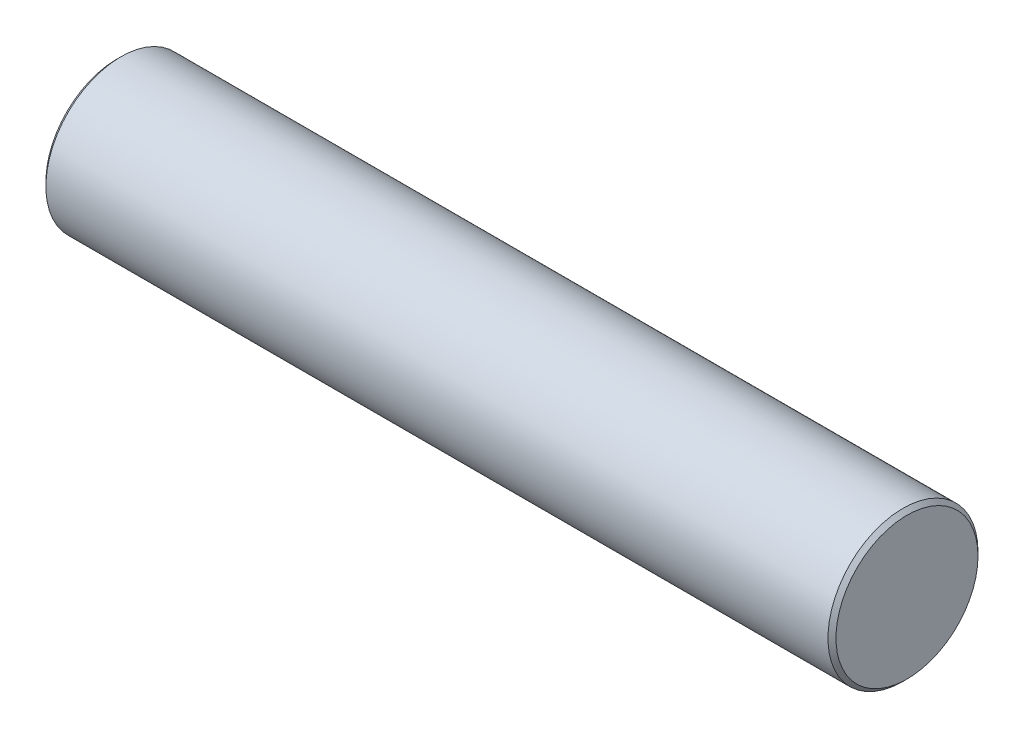
SolidWorks part; units mm, degrees
ref_plane "Front Plane" through (0, 0, 0) normal (0, 0, 1) x (1, 0, 0)
ref_plane "Top Plane" through (0, 0, 0) normal (0, 1, 0) x (1, 0, 0)
ref_plane "Right Plane" through (0, 0, 0) normal (1, 0, 0) x (0, 0, -1)
sketch "Sketch1" plane through (0, 0, 0) normal (1, 0, 0) x (0, 0, -1)
  circle A0 centre (0, 0) radius 7.5
  dimension "D1" = 15
extrude "Boss-Extrude1" add sketch "Sketch1" along normal mid plane 79
chamfer "Chamfer1" distance 0.4 angle 45 2 edges at (39.5, 0, -7.5) (-39.5, 0, -7.5)
move or copy body "Body-Move/Copy1" [suppressed] bodies to move or copy 102
